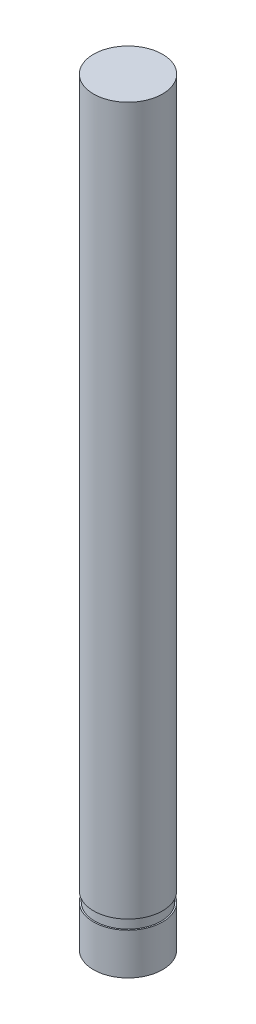
SolidWorks part; units mm, degrees
ref_plane "Front Plane" through (0, 0, 0) normal (0, 0, 1) x (1, 0, 0)
ref_plane "Top Plane" through (0, 0, 0) normal (0, 1, 0) x (1, 0, 0)
ref_plane "Right Plane" through (0, 0, 0) normal (1, 0, 0) x (0, 0, -1)
sketch "Sketch1" plane through (0, 0, 0) normal (0, 1, 0) x (1, 0, 0)
  circle A0 centre (0, 0) radius 2.5
  dimension "D1" = 5
extrude "Boss-Extrude1" add sketch "Sketch1" along normal blind 55
ref_plane "Plane1" through (0, 3, 0) normal (0, -1, 0) x (-1, 0, 0)
sketch "Sketch2" plane through (0, 3, 0) normal (0, -1, 0) x (-1, 0, 0)
  circle A0 centre (0, 0) radius 2.4
  circle A1 centre (0, 0) radius 2.5
  dimension "D1" = 4.8
  dimension "D2" = 5
extrude "Cut-Extrude1" cut sketch "Sketch2" against normal blind 0.7
